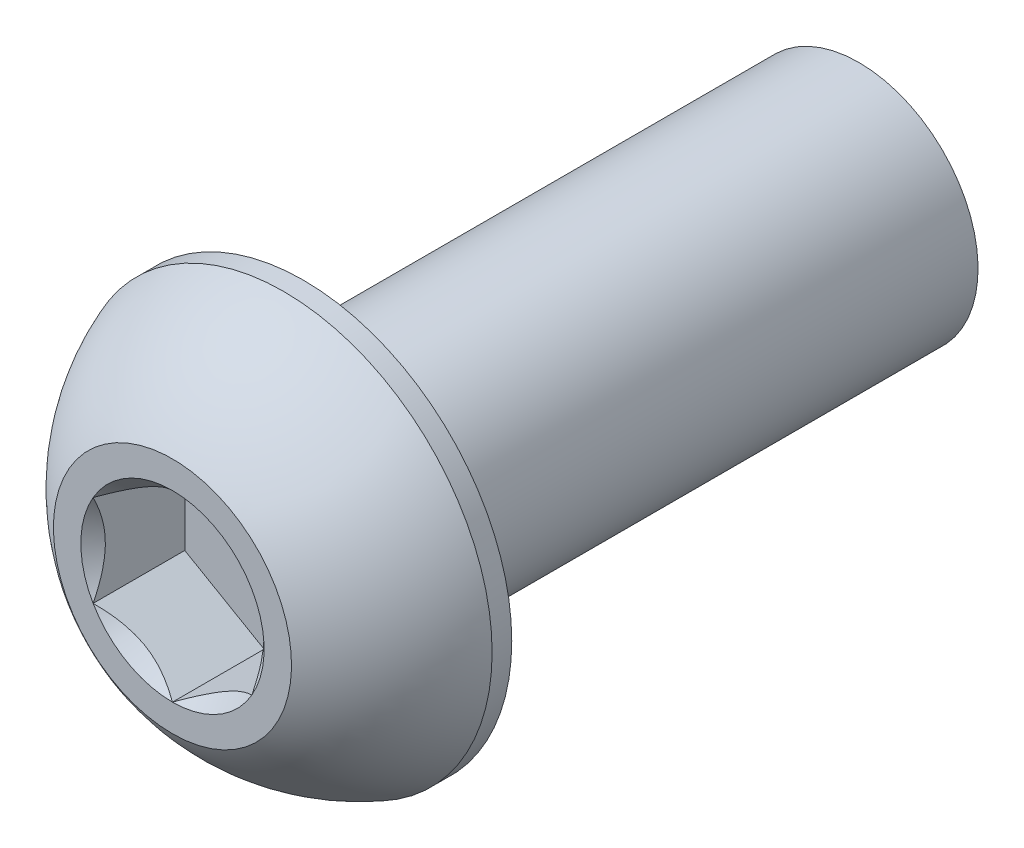
SolidWorks part; units mm, degrees
ref_plane "Front" through (0, 0, 0) normal (0, 0, 1) x (1, 0, 0)
ref_plane "Top" through (0, 0, 0) normal (0, 1, 0) x (1, 0, 0)
ref_plane "Right" through (0, 0, 0) normal (1, 0, 0) x (0, 0, -1)
sketch "Sketch1" plane through (0, 0, 0) normal (1, 0, 0) x (0, 0, -1)
  line L2 (3.3, 3) -> (17.3, 3)
  line L3 (17.3, 3) -> (17.3, 0)
  line L4 (17.3, 0) -> (3.3, 0)
  line L6 (2.805, 5.25) -> (3.3, 5.25) construction
  line L7 (17.3, 3) -> (17.3, -3) construction
  line L8 (0, 0) -> (3.3, 0) construction
  line L9 (3.3, 5.25) -> (3.3, -5.25) construction
  line L11 (3.3, 3) -> (3.3, 0)
  line L13 (0, 2) -> (0, -2) construction
  line L14 (0, 2) -> (0, 3) construction
  line L15 (17.3, -3) -> (16.3, -3) construction
  arc A3 (0, 3) -> (2.805, 5.25) centre (4.7113, 0) cw construction
  dimension "D1" = 0.495
  dimension "Pitch" = 1
revolve "Revolve1" add sketch "Sketch1" angle 360 mid plane about L4
sketch "Sketch7" plane through (0, 0, 0) normal (1, 0, 0) x (0, 0, -1)
  line L6 (2.805, 5.25) -> (3.3, 5.25) construction
  line L8 (0, 0) -> (3.3, 0) construction
  line L11 (3.3, 5.25) -> (3.3, -5.25) construction
  line L12 (2.805, 5.25) -> (3.3, 5.25)
  line L13 (0, 0) -> (3.3, 0)
  line L14 (0, 2) -> (0, -2) construction
  line L15 (3.3, 5.25) -> (3.3, 0)
  line L16 (0, 3) -> (0, 0)
  arc A2 (2.805, 5.25) -> (0, 3) centre (4.7113, 0) ccw construction
  arc A3 (2.805, 5.25) -> (0, 3) centre (4.7113, 0) ccw
revolve "Revolve2" add sketch "Sketch7" angle 360 mid plane about L13
sketch "Sketch5" plane through (0, 0, 0) normal (0, 0, 1) x (1, 0, 0)
  line L1 (2, -1.1547) -> (2, 1.1547)
  line L2 (2, 1.1547) -> (0, 2.3094)
  line L3 (0, 2.3094) -> (-2, 1.1547)
  line L4 (-2, 1.1547) -> (-2, -1.1547)
  line L5 (-2, -1.1547) -> (0, -2.3094)
  line L6 (0, -2.3094) -> (2, -1.1547)
  circle A0 centre (0, 0) radius 2 construction
extrude "Cut-Extrude2" cut sketch "Sketch5" against normal blind 2.31
sketch "Sketch6" plane through (0, 0, 0) normal (0, 0, 1) x (1, 0, 0)
  circle A0 centre (0, 0) radius 2.3094
extrude "Cut-Extrude3" cut sketch "Sketch6" against normal blind 2.31 draft 45
sketch "Sketch11" plane through (0, 0, 0) normal (1, 0, 0) x (0, 0, -1)
  line L0 (3.3, -5.25) -> (3.3, 5.25)
  point P4 (3.3, 0)
split "Split1" trim tools "Sketch11" bodies to split 113 resulting bodies 119 120
sketch "Sketch10" plane through (0, 0, 0) normal (1, 0, 0) x (0, 0, -1)
  line L0 (17.3, 3) -> (17.3, -3) construction
  point P0 (15.8, -3)
  dimension "D1" = 1.5
sketch "Sketch3" [suppressed] plane through (0, 0, -17.3) normal (0, 0, -1) x (-1, 0, 0)
  circle A0 centre (0, 0) radius 3
curve "Helix/Spiral1" [suppressed] pitch 1 height 15 turns 15
sketch "Sketch2" [suppressed] plane through (0, 0, 0) normal (1, 0, 0) x (0, 0, -1)
  line L0 (17.2375, 3.1083) -> (18.2375, 3.1083) construction
  line L1 (18.2375, 3.1083) -> (17.7375, 2.2422) construction
  line L2 (17.7375, 2.2422) -> (17.2375, 3.1083) construction
  line L3 (17.7375, 3.1083) -> (17.7375, 3) construction
  line L4 (17.7375, 3) -> (17.7375, 2.3505) construction
  line L5 (17.7375, 2.3505) -> (17.7375, 2.2422) construction
  line L6 (17.675, 2.3505) -> (17.8, 2.3505)
  line L7 (17.3, 3) -> (18.175, 3) construction
  line L8 (17.2688, 3.0541) -> (18.2063, 3.0541)
  line L9 (17.2688, 3.0541) -> (17.675, 2.3505)
  line L10 (18.2063, 3.0541) -> (17.8, 2.3505)
  point P10 (17.7375, 2.3505)
  point P13 (17.7375, 3)
  point P16 (17.7375, 3.0541)
  dimension "D1" = 1
  dimension "D2" = 0.125
chamfer "Chamfer1" [suppressed] distance 0.75 angle 45
sweep "Cut-Sweep1" [suppressed] cut profiles "Sketch2" path "Helix/Spiral1"
combine bodies "Combine1" [suppressed] operation type add bodies to combine 120 114
equation "\"D3@Helix/Spiral1\" = \"Lg@Sketch1\" + \"D4@Helix/Spiral1\""
equation "\"D1@Chamfer1\" = \"D4@Helix/Spiral1\" * .75"
equation "\"D1@Cut-Extrude2\" = \"Head Ht@Sketch1\" * .7"
equation "\"D1@Sketch1\" = \"Head Ht@Sketch1\" * .15"
equation "\"D1@Sketch10\" = \"D4@Helix/Spiral1\" * 1.5"
equation "\"D1@Cut-Extrude3\" = \"D1@Cut-Extrude2\""
equation "\"D4@Helix/Spiral1\"=\"Pitch@Sketch1\""
equation "\"D1@Sketch2\"=\"Pitch@Sketch1\""
equation "\"D2@Sketch2\"=\"D1@Sketch2\"/8"
